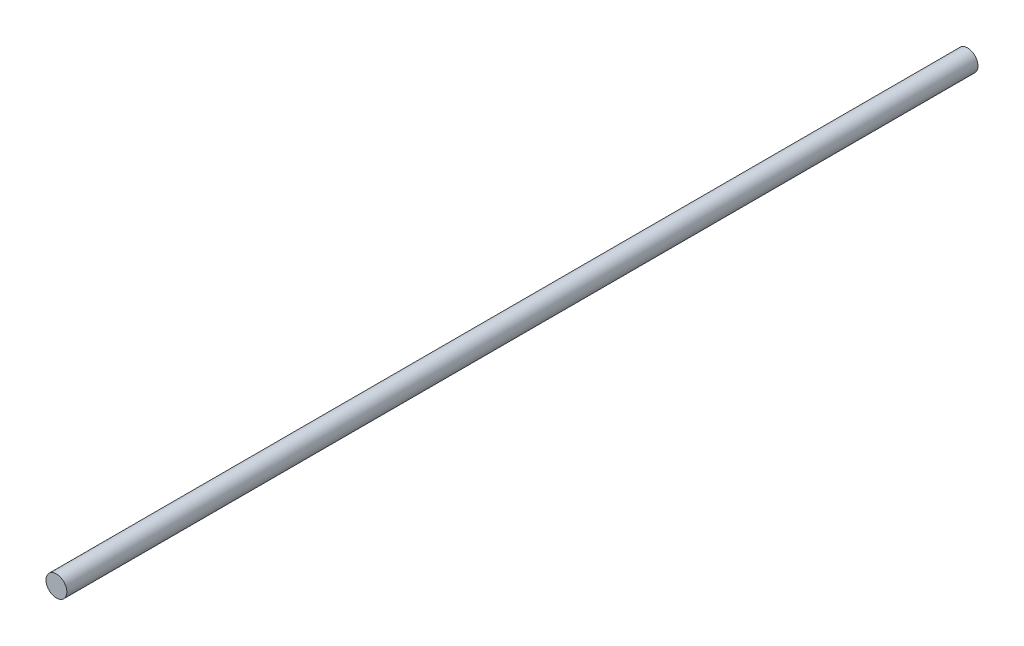
SolidWorks part; units mm, degrees
ref_plane "Front Plane" through (0, 0, 0) normal (0, 0, 1) x (1, 0, 0)
ref_plane "Top Plane" through (0, 0, 0) normal (0, 1, 0) x (1, 0, 0)
ref_plane "Right Plane" through (0, 0, 0) normal (1, 0, 0) x (0, 0, -1)
sketch "Sketch1" plane through (0, 0, 0) normal (0, 0, 1) x (1, 0, 0)
  circle A0 centre (0, 0) radius 6
  dimension "D1" = 12
extrude "Boss-Extrude1" add sketch "Sketch1" along normal mid plane 524
